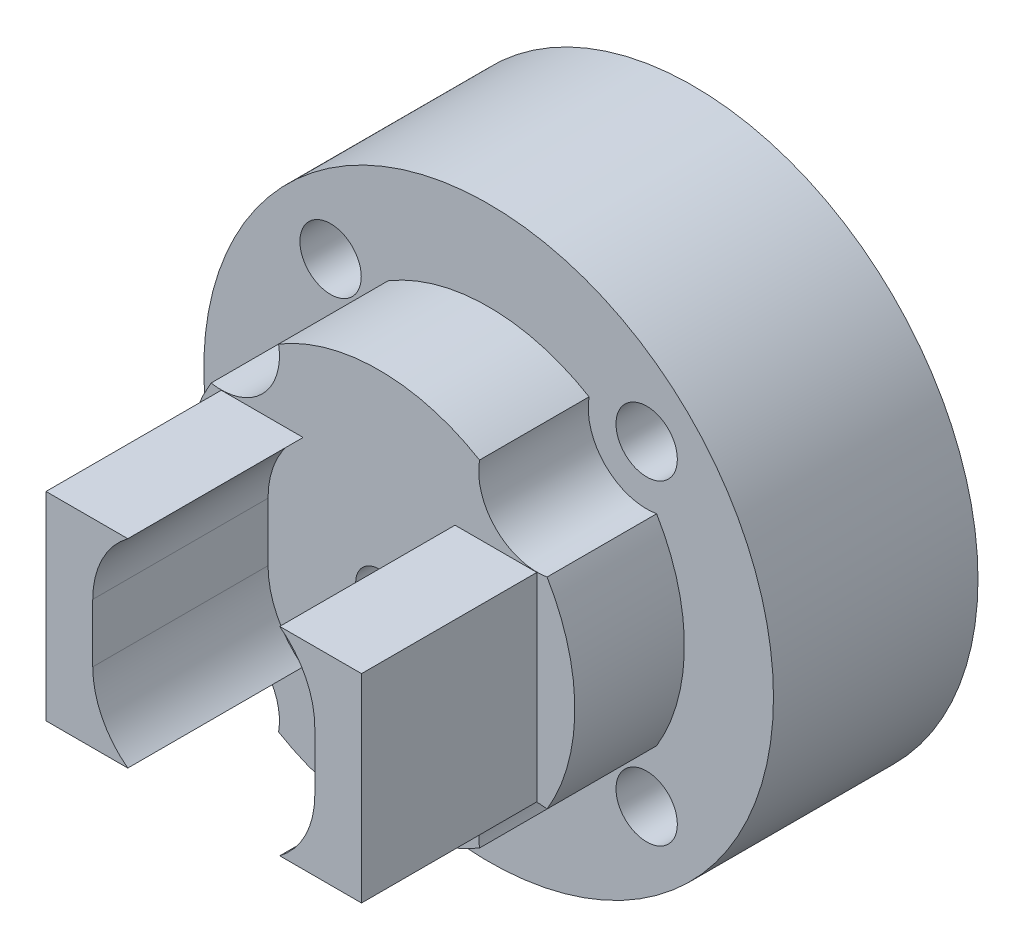
SolidWorks part; units mm, degrees
material "3.1325 (EN-AW 2017A)"
ref_plane "Ebene vorne" through (0, 0, 0) normal (0, 0, 1) x (1, 0, 0)
ref_plane "Ebene oben" through (0, 0, 0) normal (0, 1, 0) x (1, 0, 0)
ref_plane "Ebene rechts" through (0, 0, 0) normal (1, 0, 0) x (0, 0, -1)
sketch "Skizze1" plane through (0, 0, 0) normal (0, 0, 1) x (1, 0, 0)
  circle A0 centre (0, 0) radius 6.7
  circle A1 centre (0, 0) radius 3.55
  circle A2 centre (0, 0) radius 9.75
  dimension "D1" = 7.1
  dimension "D2" = 13.4
  dimension "D3" = 19.5
extrude "Aufsatz-Linear austragen1" add sketch "Skizze1" along normal blind 3.75 contours A0
extrude "Aufsatz-Linear austragen2" add sketch "Skizze1<7>" against normal blind 7 contours A2 | A1
sketch "Skizze1<7>" plane through (0, 0, 0) normal (0, 0, 1) x (1, 0, 0) same geometry as "Skizze1"
sketch "Skizze5" plane through (0, 0, 3.75) normal (0, 0, 1) x (1, 0, 0)
  line L0 (-5.4094, 5.4094) -> (5.4094, -5.4094) construction
  line L1 (0, 9.75) -> (0, -9.75) construction
  line L2 (5.4094, 5.4094) -> (-5.4094, -5.4094) construction
  circle A0 centre (5.4094, 5.4094) radius 1.05
  circle A1 centre (5.4094, -5.4094) radius 1.05
  circle A2 centre (-5.4094, -5.4094) radius 1.05
  circle A3 centre (-5.4094, 5.4094) radius 1.05
  circle A4 centre (0, 0) radius 9.75 construction
  circle A5 centre (-5.4094, 5.4094) radius 2
  circle A6 centre (5.4094, 5.4094) radius 2
  circle A7 centre (5.4094, -5.4094) radius 2
  circle A8 centre (-5.4094, -5.4094) radius 2
  dimension "D1" = 2.1
  dimension "D4" = 4
  dimension "D2" = 15.3
  dimension "D3" = 45
extrude "Schnitt-Linear austragen1" cut sketch "Skizze5" against normal through all contours A3 | A0 | A1 | A2
extrude "Schnitt-Linear austragen2" cut sketch "Skizze5<3>" against normal up to surface (3.75 mm away) up to face at (0, 0, 0)
sketch "Skizze5<3>" plane through (0, 0, 3.75) normal (0, 0, 1) x (1, 0, 0) same geometry as "Skizze5"
chamfer "Fase1" distance 0.3 angle 45 1 edges at (3.55, 0, -7)
sketch "Skizze7" plane through (0, 0, 3.75) normal (0, 0, 1) x (1, 0, 0)
  line L0 (-5.4, 0) -> (-3.8, 0) construction
  line L1 (-5.4, 3.4) -> (-2.6, 3.4)
  line L2 (-5.4, 3.4) -> (-5.4, -3.4)
  line L3 (-5.4, -3.4) -> (-2.6, -3.4)
  line L4 (-3.8, 1) -> (-3.8, -1)
  line L5 (0, 6.7) -> (0, -6.7) construction
  line L6 (-3.8, 0) -> (3.8, 0) construction
  line L7 (5.4, -3.4) -> (2.6, -3.4)
  line L8 (3.8, 1) -> (3.8, -1)
  line L9 (5.4, 3.4) -> (5.4, -3.4)
  line L10 (5.4, 3.4) -> (2.6, 3.4)
  arc A0 (-3.8, -1) -> (-2.6, -3.4) centre (-0.8, -1) ccw
  arc A1 (-3.8, 1) -> (-2.6, 3.4) centre (-0.8, 1) cw
  arc A2 (3.4386, 5.7503) -> (-3.4386, 5.7503) centre (0, 0) ccw construction
  arc A3 (-3.4386, -5.7503) -> (3.4386, -5.7503) centre (0, 0) ccw construction
  arc A4 (3.8, -1) -> (2.6, -3.4) centre (0.8, -1) cw
  arc A5 (3.8, 1) -> (2.6, 3.4) centre (0.8, 1) ccw
  dimension "D1" = 1.6
  dimension "D4" = 3
  dimension "D2" = 7.6
  dimension "D3" = 6.8
  dimension "D5" = 2
extrude "Aufsatz-Linear austragen4" add sketch "Skizze7" along normal blind 6 contours L2 L1 | L2 L3 | A5 L8 A4 L7 L9 L10 region at (-4.4428, 0, 3.75) region at (4.4428, 0, 3.75)
hole_wizard "M2 Gewindebohrung1" positions "Skizze9" profile "Skizze8" tap size "M2" standard "DIN" end condition through all
sketch "Skizze9" plane through (0, 0, 3.75) normal (0, 0, 1) x (1, 0, 0)
  point P0 (0, 0)
sketch "Skizze8" plane through (0, 0, 3.75) normal (1, 0, 0) x (0, -1, 0)
  line L0 (0, 0) -> (0, 10.75)
  line L1 (0, 10.75) -> (0.8, 10.75)
  line L2 (0.8, 10.75) -> (0.8, 0)
  line L5 (0.8, 0) -> (0, 0)
  line L11 (0, -6.35) -> (0, 107.95) construction
  dimension "Bohrerdurchmesser" = 1.6
  dimension "Bohrungstiefe" = 10.75
cosmetic thread "Bohrungsgewinde3" parameters "D1"=7.75, "D2"=2
